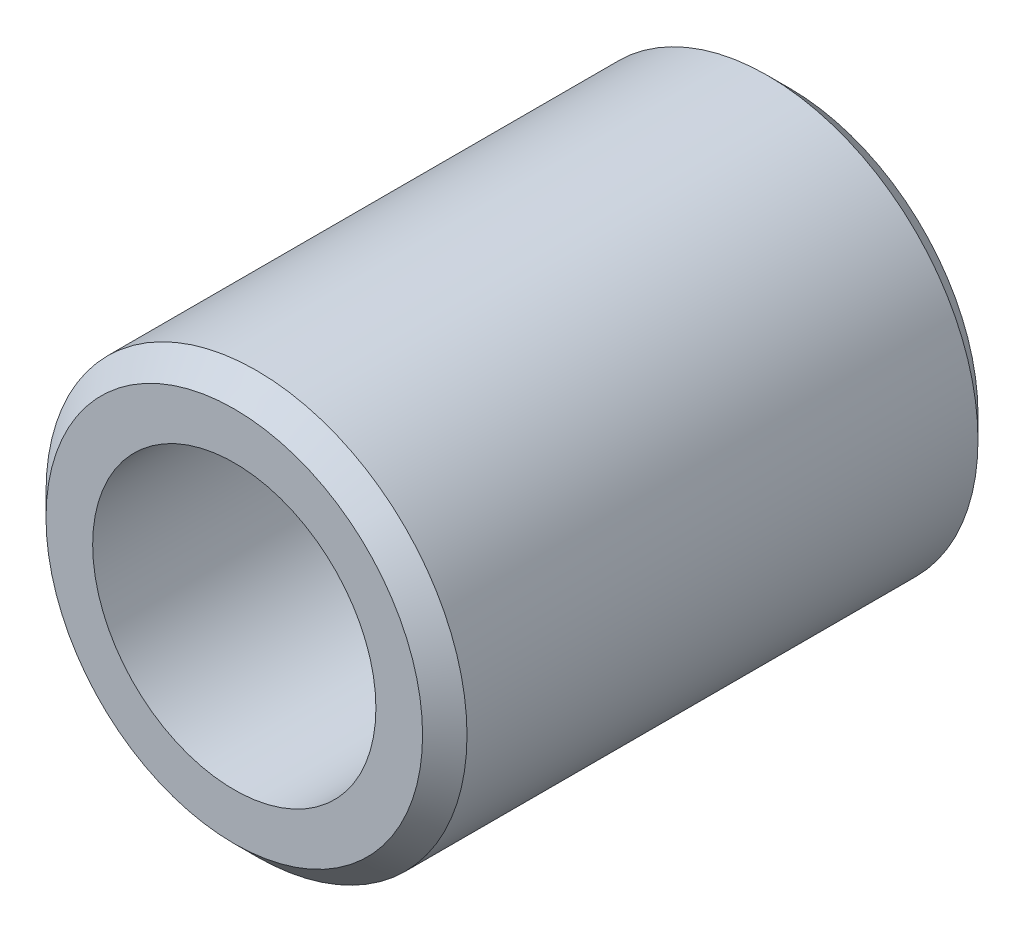
SolidWorks part; units mm, degrees
material "Brass"
ref_plane "Front Plane" through (0, 0, 0) normal (0, 0, 1) x (1, 0, 0)
ref_plane "Top Plane" through (0, 0, 0) normal (0, 1, 0) x (1, 0, 0)
ref_plane "Right Plane" through (0, 0, 0) normal (1, 0, 0) x (0, 0, -1)
sketch "Sketch1" plane through (0, 0, 0) normal (1, 0, 0) x (0, 0, -1)
  line L0 (-3.175, 2.1526) -> (-3.175, 1.6193)
  line L1 (-3.175, 1.6193) -> (3.175, 1.6193)
  line L2 (3.175, 1.6193) -> (3.175, 2.1526)
  line L3 (3.175, 2.1526) -> (2.921, 2.4067)
  line L4 (2.921, 2.4067) -> (-2.921, 2.4067)
  line L5 (-2.921, 2.4067) -> (-3.175, 2.1526)
  line L6 (3.175, 0) -> (-3.175, 0) construction
revolve "Revolve1" add sketch "Sketch1" angle 360 about L6 reverse direction yes
ref_plane "bushing XY" through (0, 0, 0) normal (0, 0, 1) x (1, 0, 0)
ref_plane "bushing XZ" through (0, 0, 0) normal (0, -1, 0) x (-1, 0, 0)
ref_plane "bushing YZ" through (0, 0, 0) normal (1, 0, 0) x (0, 0, -1)
ref_axis "bushing X" through (-80.9, 0, 0) along (1, 0, 0)
ref_axis "bushing Y" through (0, -50, 0) along (0, 1, 0)
ref_axis "bushing Z" through (0, 0, 80.9) along (0, 0, -1)
sketch3d "bushing"
  point P0 (0, 0, 0)
ref_plane "id1 XY" through (0, 0, 0) normal (0, 0, 1) x (1, 0, 0)
ref_plane "id1 XZ" through (0, 0, 0) normal (0, -1, 0) x (-1, 0, 0)
ref_plane "id1 YZ" through (-1.6193, 0, 0) normal (1, 0, 0) x (0, 0, -1)
ref_axis "id1 X" through (-80.9, 0, 0) along (1, 0, 0)
ref_axis "id1 Y" through (-1.6193, -50, 0) along (0, 1, 0)
ref_axis "id1 Z" through (-1.6193, 0, 80.9) along (0, 0, -1)
sketch3d "id1"
  point P0 (-1.6193, 0, 0)
ref_plane "id2 XY" through (0, 0, 0) normal (0, 0, 1) x (1, 0, 0)
ref_plane "id2 XZ" through (0, 0, 0) normal (0, -1, 0) x (-1, 0, 0)
ref_plane "id2 YZ" through (1.6193, 0, 0) normal (1, 0, 0) x (0, 0, -1)
ref_axis "id2 X" through (-80.9, 0, 0) along (1, 0, 0)
ref_axis "id2 Y" through (1.6193, -50, 0) along (0, 1, 0)
ref_axis "id2 Z" through (1.6193, 0, 80.9) along (0, 0, -1)
sketch3d "id2"
  point P0 (1.6193, 0, 0)
ref_plane "id3 XY" through (0, 0, -3.175) normal (0, 0, -1) x (-1, 0, 0)
ref_plane "id3 XZ" through (0, 0, 0) normal (-1, 0, 0) x (0, 0, 1)
ref_plane "id3 YZ" through (0, 0, 0) normal (0, 1, 0) x (1, 0, 0)
ref_axis "id3 X" through (0, -50, -3.175) along (0, 1, 0)
ref_axis "id3 Y" through (-80.9, 0, -3.175) along (1, 0, 0)
ref_axis "id3 Z" through (0, 0, -50) along (0, 0, 1)
sketch3d "id3"
  point P0 (0, 0, -3.175)
ref_plane "id4 XY" through (0, 0, 3.175) normal (0, 0, 1) x (1, 0, 0)
ref_plane "id4 XZ" through (0, 0, 0) normal (1, 0, 0) x (0, 0, -1)
ref_plane "id4 YZ" through (0, 0, 0) normal (0, 1, 0) x (1, 0, 0)
ref_axis "id4 X" through (0, -50, 3.175) along (0, 1, 0)
ref_axis "id4 Y" through (80.9, 0, 3.175) along (-1, 0, 0)
ref_axis "id4 Z" through (0, 0, 50) along (0, 0, -1)
sketch3d "id4"
  point P0 (0, 0, 3.175)
